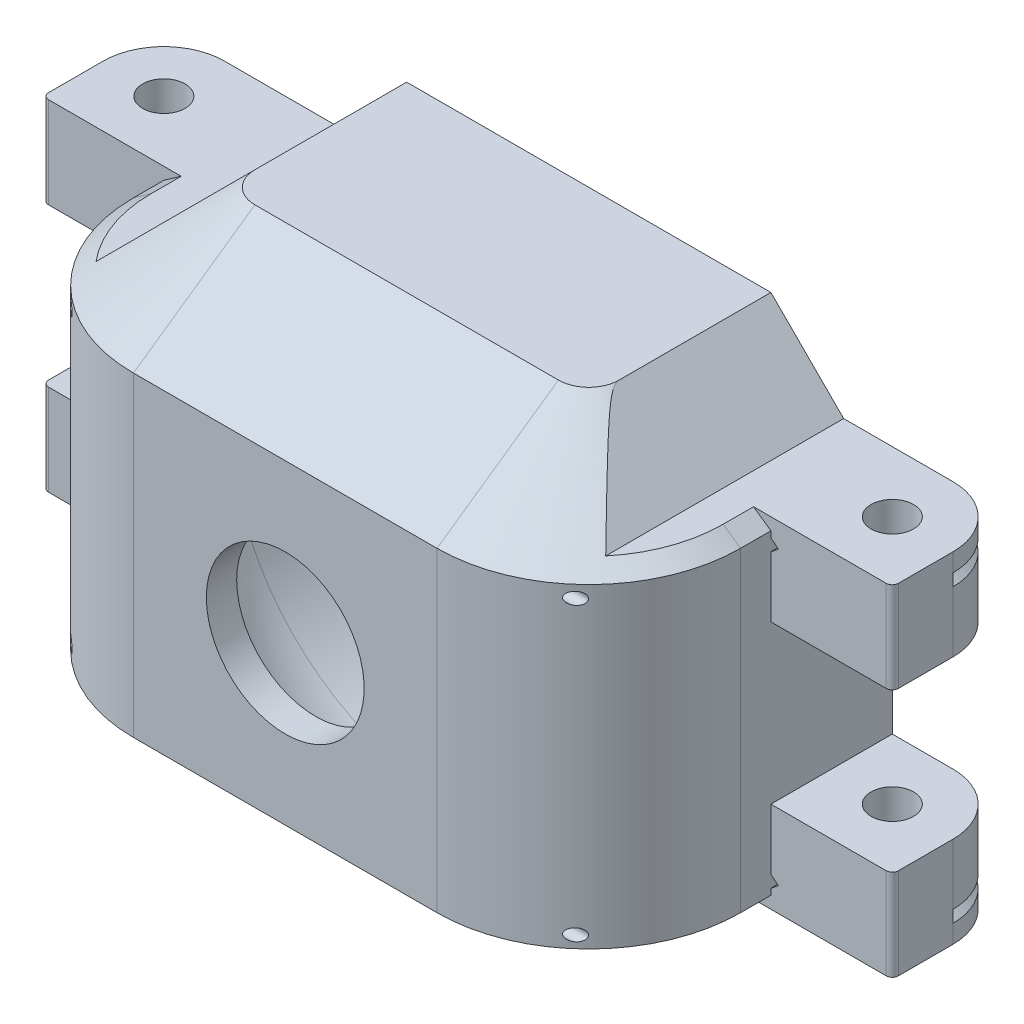
SolidWorks part; units mm, degrees
ref_plane "Front Plane" through (0, 0, 0) normal (0, 0, 1) x (1, 0, 0)
ref_plane "Top Plane" through (0, 0, 0) normal (0, 1, 0) x (1, 0, 0)
ref_plane "Right Plane" through (0, 0, 0) normal (1, 0, 0) x (0, 0, -1)
sketch "Sketch3" plane through (0, 0, 0) normal (0, 1, 0) x (1, 0, 0)
  line L0 (-3.2653, 27.8512) -> (-3.2653, -14.7845) construction
  line L4 (21.7347, 5.6122) -> (21.7347, 3.1122)
  line L5 (21.7347, 15.6122) -> (26.7347, 15.6122)
  line L7 (21.7347, 5.6122) -> (31.2347, 5.6122)
  line L8 (31.7347, 10.6122) -> (31.7347, 6.1122)
  line L9 (-38.2653, 10.6122) -> (-38.2653, 6.1122)
  line L10 (-28.2653, 5.6122) -> (-37.7653, 5.6122)
  line L11 (-28.2653, 15.6122) -> (-33.2653, 15.6122)
  line L12 (-28.2653, 5.6122) -> (-28.2653, 3.1122)
  line L13 (21.7347, 5.6122) -> (21.7347, 15.6122) construction
  line L14 (-15.7653, -9.3878) -> (-3.2653, -9.3878)
  line L15 (9.2347, -9.3878) -> (-3.2653, -9.3878)
  line L16 (21.7347, 15.6122) -> (-3.2653, 15.6122)
  line L17 (-3.2653, 15.6122) -> (-28.2653, 15.6122)
  circle A0 centre (26.7347, 10.6122) radius 1.75
  arc A1 (26.7347, 15.6122) -> (31.7347, 10.6122) centre (26.7347, 10.6122) cw
  arc A2 (31.2347, 5.6122) -> (31.7347, 6.1122) centre (31.2347, 6.1122) ccw
  arc A3 (9.2347, -9.3878) -> (21.7347, 3.1122) centre (9.2347, 3.1122) ccw
  arc A4 (-15.7653, -9.3878) -> (-28.2653, 3.1122) centre (-15.7653, 3.1122) cw
  arc A5 (-37.7653, 5.6122) -> (-38.2653, 6.1122) centre (-37.7653, 6.1122) cw
  arc A6 (-33.2653, 15.6122) -> (-38.2653, 10.6122) centre (-33.2653, 10.6122) ccw
  circle A7 centre (-33.2653, 10.6122) radius 1.75
  point P0 (-3.2653, 15.6122)
  point P28 (-3.2653, -9.3878)
  dimension "D5" = 3.5
  dimension "D3" = 0.5
  dimension "D2" = 12.5
  dimension "D1" = 12.5
  dimension "D4" = 5
  dimension "D6" = 5
  dimension "D7" = 5
extrude "Boss-Extrude1" add sketch "Sketch3" along normal blind 40
sketch "Sketch4" plane through (0, 0, -15.6122) normal (0, 0, -1) x (-1, 0, 0)
  line L5 (3.2653, 0) -> (3.2653, 40) construction
  line L7 (-26.7347, 0) -> (33.2653, 0) construction
  line L10 (38.2653, 13.5) -> (28.2653, 13.5)
  line L11 (-31.7347, 26.5) -> (-21.7347, 26.5)
  line L12 (-31.7347, 26.5) -> (-31.7347, 13.5)
  line L13 (-31.7347, 13.5) -> (-21.7347, 13.5)
  line L14 (-21.7347, 26.5) -> (-21.7347, 13.5)
  line L15 (28.2653, 26.5) -> (28.2653, 13.5)
  line L16 (38.2653, 26.5) -> (28.2653, 26.5)
  line L17 (38.2653, 26.5) -> (38.2653, 13.5)
  line L18 (-26.7347, 40) -> (33.2653, 40) construction
  line L19 (-31.7347, 20) -> (38.2653, 20) construction
  dimension "D2" = 13
  dimension "D4" = 10
extrude "Cut-Extrude1" cut sketch "Sketch4" against normal blind 10
ref_axis "Axis1" through (-33.2653, 13.5, -10.6122) along (0, -1, 0)
ref_plane "Plane1" through (0, 0, -10.6122) normal (0, 0, 1) x (1, 0, 0)
sketch "Sketch7" plane through (0, 0, -10.6122) normal (0, 0, 1) x (1, 0, 0)
  line L0 (-33.2653, 7.5) -> (-38.2653, 7.5) construction
  line L7 (-38.2653, 7.5) -> (-38.2653, 8.5) construction
  line L8 (-38.2653, 13.5) -> (-38.2653, 0) construction
  line L9 (-38.2653, 8.5) -> (-33.2653, 8.5) construction
  line L11 (-33.2653, 8.5) -> (-33.2653, 7.5) construction
  line L16 (-35.7653, 8.5) -> (-35.7653, 7.5) construction
  line L21 (-38.2653, 8.5) -> (-35.7653, 7.5) construction
  line L22 (-38.2653, 7.5) -> (-35.7653, 8.5) construction
  line L23 (-37.0153, 8) -> (-37.0153, 8.5) construction
  line L24 (-37.0153, 8.5) -> (-38.2653, 7.5) construction
  line L25 (-37.0153, 8) -> (-37.0153, 7.5) construction
  line L26 (-38.2653, 8.5) -> (-37.0153, 7.5) construction
  line L27 (-38.2653, 7.5) -> (-37.6403, 8)
  line L28 (-37.6403, 8) -> (-38.2653, 8.5)
  line L29 (-38.2653, 8.5) -> (-38.2653, 7.5)
  line L30 (-28.2653, 13.5) -> (-37.7653, 13.5) construction
  dimension "D1" = 1
  dimension "D2" = 2.5
  dimension "D3" = 5
revolve "Cut-Revolve1" cut sketch "Sketch7" angle 180 about axis through (-33.2653, 13.5, -10.6122) along (0, -1, 0)
sketch "Sketch9" plane through (0, 0, -5.6122) normal (0, 0, 1) x (1, 0, 0)
  line L0 (-38.2653, 13.5) -> (-28.2653, 13.5) construction
  line L7 (-37.7653, 13.5) -> (-38.2653, 13.5) construction
  line L8 (-28.2653, 13.5) -> (-28.2653, 0) construction
  line L9 (-28.2653, 0) -> (-38.2653, 0) construction
  line L11 (-38.2653, 13.5) -> (-38.2653, 0) construction
  line L16 (-33.2653, 13.5) -> (-33.2653, 0) construction
  line L33 (-38.2653, 7.5) -> (-33.2653, 7.5) construction
  line L34 (-35.7653, 7.5) -> (-35.7653, 0) construction
  line L35 (-33.2653, 8.5) -> (-38.2653, 8.5) construction
  line L36 (-38.2653, 8.5) -> (-33.2653, 7.5) construction
  line L37 (-38.2653, 7.5) -> (-33.2653, 8.5) construction
  line L38 (-35.7653, 8) -> (-35.7653, 8.5) construction
  line L39 (-35.7653, 8) -> (-35.7653, 7.5) construction
  line L40 (-35.7653, 8.5) -> (-38.2653, 7.5) construction
  line L41 (-35.7653, 7.5) -> (-38.2653, 8.5) construction
  line L48 (-37.0153, 8) -> (-37.0153, 8.5) construction
  line L49 (-37.0153, 8) -> (-37.0153, 7.5) construction
  line L50 (-38.2653, 7.5) -> (-37.0153, 8.5) construction
  line L51 (-38.2653, 8.5) -> (-37.0153, 7.5) construction
  line L52 (-38.2653, 8.5) -> (-37.6403, 8) construction
  line L53 (-37.6403, 8) -> (-38.2653, 7.5) construction
  line L54 (-38.2653, 7.5) -> (-38.2653, 8.5) construction
  line L55 (-28.8903, 8) -> (-28.2653, 7.5)
  line L56 (-28.2653, 8.5) -> (-28.8903, 8)
  line L57 (-28.2653, 7.5) -> (-28.2653, 8.5)
  dimension "D1" = 5
  dimension "D2" = 1
extrude "Cut-Extrude2" cut sketch "Sketch9" against normal blind 5
sketch "Sketch10" plane through (-28.2653, 0, 0) normal (-1, 0, 0) x (0, 0, 1)
  line L0 (-5.6122, 13.5) -> (9.3878, 13.5) construction
  line L5 (-3.1122, 40) -> (9.3878, 40) construction
  line L6 (-3.1122, 40) -> (-3.1122, 0) construction
  line L7 (-3.1122, 0) -> (9.3878, 0) construction
  line L8 (9.3878, 40) -> (9.3878, 0) construction
  line L9 (9.3414, 8.5) -> (3.1378, 7.5) construction
  line L10 (-3.1122, 0) -> (9.3878, 13.5) construction
  line L11 (3.1378, 6.75) -> (3.1378, 13.5) construction
  line L12 (9.3878, 7.5) -> (3.1378, 8.5) construction
  line L13 (3.1378, 6.75) -> (3.1378, 0) construction
  line L14 (9.3878, 8.5) -> (3.1378, 8.5) construction
  line L15 (9.3878, 7.5) -> (-3.1122, 7.5) construction
  circle A0 centre (6.2396, 8) radius 0.5
  dimension "D1" = 5
  dimension "D2" = 1
extrude "Cut-Extrude3" cut sketch "Sketch10" against normal blind 40
ref_plane "Plane2" through (0, 20, 0) normal (0, 1, 0) x (1, 0, 0)
ref_plane "Plane3" through (-3.2653, 0, 0) normal (-1, 0, 0) x (0, 0, 1)
mirror "Mirror2" about plane through (0, 20, 0) normal (0, 1, 0) of "Cut-Extrude3", "Cut-Extrude2", "Cut-Revolve1"
mirror "Mirror3" about plane through (-3.2653, 0, 0) normal (-1, 0, 0) of "Mirror2"
sketch "Sketch11" plane through (0, 0, -15.6122) normal (0, 0, -1) x (-1, 0, 0)
  line L0 (-26.7347, 0) -> (33.2653, 40) construction
  line L1 (33.2653, 0) -> (-26.7347, 40) construction
  circle A0 centre (3.2653, 20) radius 18
extrude "Cut-Extrude4" cut sketch "Sketch11" against normal blind 22.5
sketch "Sketch13" plane through (0, 0, 6.8878) normal (0, 0, -1) x (-1, 0, 0)
  circle A0 centre (3.2653, 20) radius 6.5
  dimension "D1" = 13
extrude "Cut-Extrude5" cut sketch "Sketch13" against normal blind 2.5 and the other way blind 1
fillet "Fillet2" radius 11 1 edges at (-21.2653, 20, 6.8878)
chamfer "Chamfer2" distance 10 angle 35 5 edges at (-28.2653, 40, -4.3622) (21.7347, 40, -4.3622) (-24.6041, 40, 5.7266) (18.0735, 40, 5.7266) (-3.2653, 40, 9.3878) first distance on face at (26.7347, 40, -8.8622)
chamfer "Chamfer3" distance 10 angle 35 5 edges at (-28.2653, 0, -4.3622) (21.7347, 0, -4.3622) (-24.6041, 0, 5.7266) (18.0735, 0, 5.7266) (-3.2653, 0, 9.3878) first distance on face at (-3.2653, 0, -5.0898)
sketch "Sketch14" plane through (0, 0, -15.6122) normal (0, 0, -1) x (-1, 0, 0)
  line L0 (3.2653, 20) -> (3.2653, 40) construction
  line L1 (-11.7347, 40) -> (18.2653, 40)
  line L2 (-26.7347, 40) -> (33.2653, 40) construction
  line L3 (18.2653, 40) -> (24.2585, 34)
  line L4 (24.2585, 34) -> (44.6102, 34)
  line L5 (44.6102, 34) -> (44.6102, 43.9388)
  line L6 (44.6102, 43.9388) -> (-38.0795, 43.9388)
  line L8 (3.2653, 20) -> (54.5439, 20) construction
  line L9 (3.2653, 20) -> (3.2653, 0) construction
  line L10 (44.6102, -3.9388) -> (-38.0795, -3.9388)
  line L11 (44.6102, 6) -> (44.6102, -3.9388)
  line L12 (24.2585, 6) -> (44.6102, 6)
  line L13 (18.2653, 0) -> (24.2585, 6)
  line L14 (-11.7347, 0) -> (18.2653, 0)
  line L16 (-38.0795, 6) -> (-38.0795, -3.9388)
  line L17 (-17.7279, 6) -> (-34.3097, 6)
  line L18 (-11.7347, 0) -> (-17.7279, 6)
  line L19 (-38.0795, 34) -> (-38.0795, 43.9388)
  line L20 (-17.7279, 34) -> (-34.3097, 34)
  line L21 (-11.7347, 40) -> (-17.7279, 34)
  line L22 (-38.0795, 34) -> (-38.0795, 6)
  line L23 (-34.3097, 6) -> (-34.3097, 34)
  line L24 (3.2653, 43.9388) -> (3.2653, 52.7169) construction
  line L25 (3.2653, -3.9388) -> (3.2653, -5.4052) construction
  dimension "D1" = 15
  dimension "D2" = 6
extrude "Cut-Extrude6" cut sketch "Sketch14" against normal blind 20
